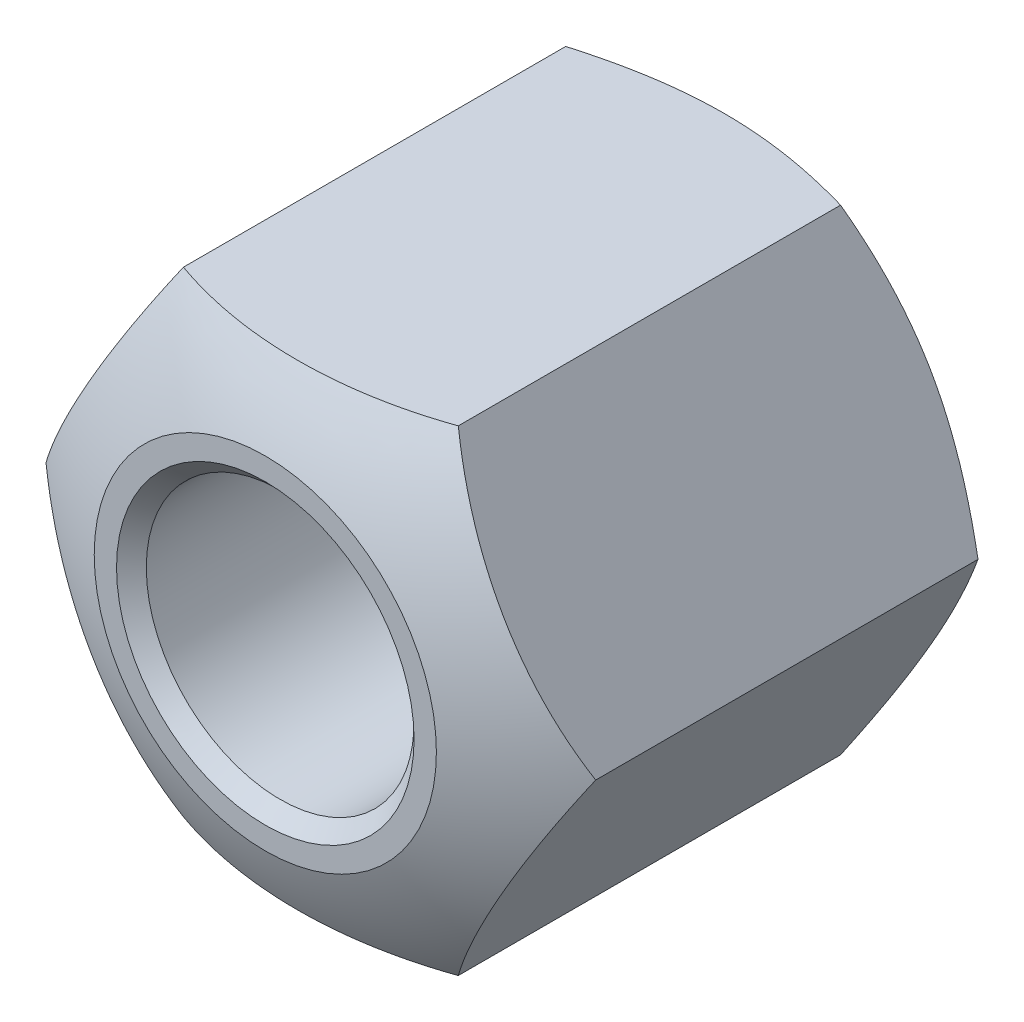
SolidWorks part; units mm, degrees
ref_plane "Front" through (0, 0, 0) normal (0, 0, 1) x (1, 0, 0)
ref_plane "Top" through (0, 0, 0) normal (0, 1, 0) x (1, 0, 0)
ref_plane "Right" through (0, 0, 0) normal (1, 0, 0) x (0, 0, -1)
sketch "Sketch1" plane through (0, 0, 0) normal (0, 0, 1) x (1, 0, 0)
  line L1 (4.6188, -8) -> (9.2376, 0)
  line L2 (9.2376, 0) -> (4.6188, 8)
  line L3 (4.6188, 8) -> (-4.6188, 8)
  line L4 (-4.6188, 8) -> (-9.2376, 0)
  line L5 (-9.2376, 0) -> (-4.6188, -8)
  line L6 (-4.6188, -8) -> (4.6188, -8)
  circle A0 centre (0, 0) radius 8 construction
  circle A1 centre (0, 0) radius 4.5
  dimension "D1" = 9
extrude "BaseNut" add sketch "Sketch1" against normal blind 16.35
cosmetic thread "ThreadCosmetic1" [suppressed] parameters "D2"=10
sketch "Sketch2" plane through (-4.3776, 0, -4.86) normal (0, 1, 0) x (0, 0, 1)
  line L0 (-10.092, 4.3776) -> (10.5743, 4.3776) construction
  line L4 (2.9928, 13.6152) -> (4.86, 13.6152)
  line L5 (4.86, 13.6152) -> (4.86, 10.1276)
  arc A0 (2.9928, 13.6152) -> (4.86, 10.1276) centre (-10.0711, 4.3776) cw
  dimension "R" = 16
  dimension "d" = 11.5
revolve "EndChamfer1" cut sketch "Sketch2" angle 360 about L0
sketch "Sketch3" plane through (-4.6188, 0, -4.6188) normal (0, 1, 0) x (0, 0, 1)
  line L0 (9.4241, 4.6188) -> (-9.4241, 4.6188) construction
  line L1 (-11.7312, 11.0245) -> (-11.7312, 13.8564)
  line L3 (-11.7312, 13.8564) -> (-10.0962, 13.8564)
  line L5 (-10.0962, 13.8564) -> (-11.7312, 11.0245)
  dimension "D1" = 30
  dimension "D2" = 1.635
revolve "EndChamfer2" cut sketch "Sketch3" angle 360 about L0
chamfer "Chamfer1" distance 0.5 angle 45 2 edges at (4.5, 0, 0) (4.5, 0, -16.35)
sketch "Sketch4" plane through (0, 0, 0) normal (0, 1, 0) x (1, 0, 0)
  line L0 (-4.933, 0.5) -> (-4.5, 0.75)
  line L1 (-4.5, 0.75) -> (-4, 0.75)
  line L2 (-4, 0.75) -> (-4, 0.25)
  line L3 (-4, 0.25) -> (-4.5, 0.25)
  line L4 (-4.5, 0.25) -> (-4.933, 0.5)
  line L5 (0, 0) -> (0, -6.6415) construction
  line L8 (-4.5, 0.5) -> (4.5, 0.5) construction
  dimension "D1" = 0.5
  dimension "D2" = 9
revolve "Cut-Revolve10" [suppressed] cut sketch "Sketch4" angle 360 about L5
pattern_linear "LPattern10" [suppressed] count 26 spacing 0.6 along (0, 0, -1) of bodies 106
equation "\"D2@Sketch3\" = \"m@BaseNut\" /10"
equation "\"D2@Sketch4\"=\"D1@Sketch1\""
equation "\"D1@Sketch4\"= (\"D2@ThreadCosmetic1\" -\"D2@Sketch4\"  )  / 2"
equation "\"D3@LPattern10\"=\"D1@Sketch4\" * 1.2"
equation "\"D1@Chamfer1\" =  ( \"D2@ThreadCosmetic1\" - \"D1@Sketch1\" )  / 2"
equation "\"D1@LPattern10\"= ( \"m@BaseNut\" - \"D1@Chamfer1\" )  / \"D3@LPattern10\""
